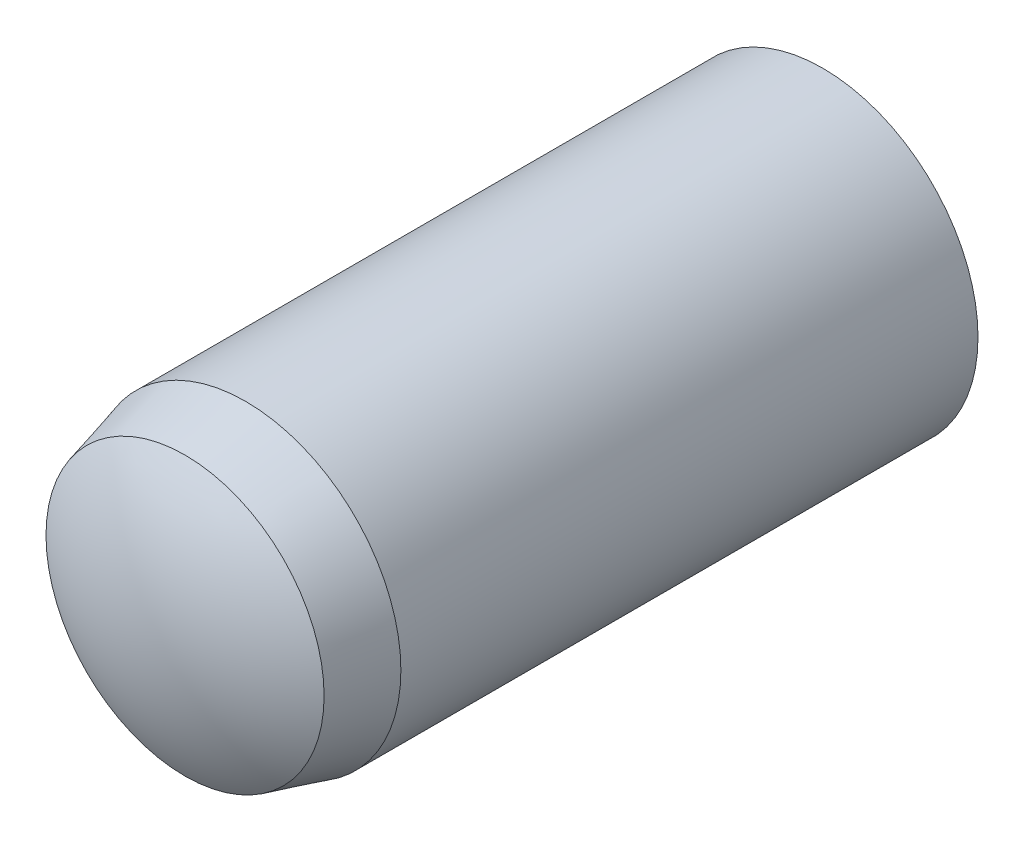
SolidWorks part; units mm, degrees
ref_plane "Front Plane" through (0, 0, 0) normal (0, 0, 1) x (1, 0, 0)
ref_plane "Top Plane" through (0, 0, 0) normal (0, 1, 0) x (1, 0, 0)
ref_plane "Right Plane" through (0, 0, 0) normal (1, 0, 0) x (0, 0, -1)
sketch "Sketch1" plane through (0, 0, 0) normal (0, 0, 1) x (1, 0, 0)
  circle A0 centre (0, 0) radius 3
  point P3 (0, 3)
  dimension "Diameter" = 6
sketch "Sketch2" plane through (0, 0, 0) normal (1, 0, 0) x (0, 0, -1)
  line L0 (-7, 0) -> (7, 0) construction
  line L1 (-7, 0) -> (-7, 3) construction
  line L2 (-7, 3) -> (7, 3)
  line L3 (7, 3) -> (7, 0) construction
  line L4 (-6.22, 2.6865) -> (-5.05, 3)
  arc A0 (-7, 0) -> (-6.22, 2.6865) centre (-1.9835, 0) cw
  arc A1 (7, 0) -> (6.1, 3) centre (1.55, 0) ccw
  point P2 (0, 0)
  dimension "D1" = 15
  dimension "D2" = 0.9
  dimension "D3" = 1.95
  dimension "D4" = 1.17
sketch "Sketch3" plane through (0, 0, 0) normal (1, 0, 0) x (0, 0, -1)
  line L0 (-7, 0) -> (7, 0) construction
  line L1 (-6.22, 2.6865) -> (-5.05, 3) construction
  line L2 (-7, 0) -> (7, 0)
  line L3 (-6.22, 2.6865) -> (-5.05, 3)
  line L4 (-5.05, 3) -> (6.1, 3)
  arc A0 (7, 0) -> (6.1, 3) centre (1.55, 0) ccw construction
  arc A1 (-6.22, 2.6865) -> (-7, 0) centre (-1.9835, 0) ccw construction
  arc A2 (7, 0) -> (6.1, 3) centre (1.55, 0) ccw
  arc A3 (-6.22, 2.6865) -> (-7, 0) centre (-1.9835, 0) ccw
revolve "Revolve1" add sketch "Sketch3" angle 360 about L2
equation "\"D2@Sketch2\" = \"Diameter@Sketch1\" * .15"
equation "\"D3@Sketch2\" = \"Diameter@Sketch1\" * .325"
equation "\"D4@Sketch2\" = \"D3@Sketch2\" * .6"
